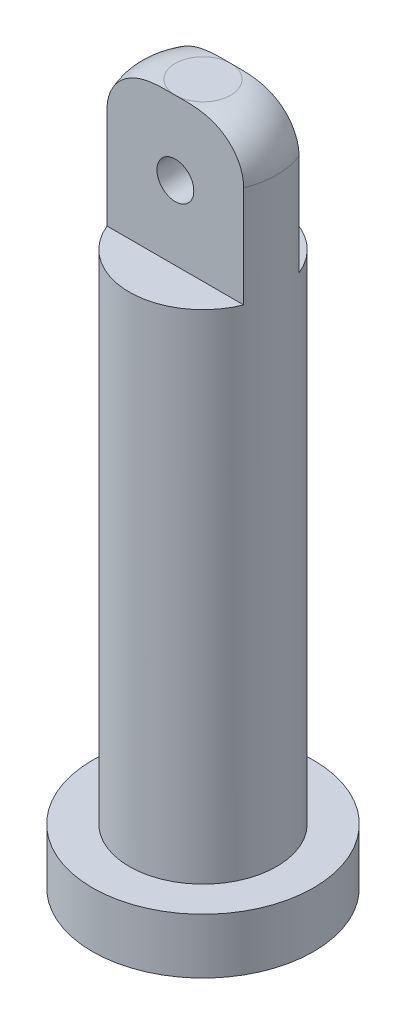
SolidWorks part; units mm, degrees
ref_plane "Front Plane" through (0, 0, 0) normal (0, 0, 1) x (1, 0, 0)
ref_plane "Top Plane" through (0, 0, 0) normal (0, 1, 0) x (1, 0, 0)
ref_plane "Right Plane" through (0, 0, 0) normal (1, 0, 0) x (0, 0, -1)
sketch "Sketch1" plane through (0, 0, 0) normal (0, 1, 0) x (1, 0, 0)
  circle A0 centre (0, 0) radius 3
  dimension "D1" = 6
extrude "Boss-Extrude1" add sketch "Sketch1" along normal blind 1.5
sketch "Sketch2" plane through (0, 1.5, 0) normal (0, 1, 0) x (1, 0, 0)
  circle A0 centre (0, 0) radius 2
  dimension "D1" = 4
extrude "Boss-Extrude2" add sketch "Sketch2" along normal blind 13.5
sketch "Sketch6" plane through (0, 15, 0) normal (0, 1, 0) x (1, 0, 0)
  line L1 (1.854, 0.75) -> (-1.854, 0.75)
  line L3 (1.854, -0.75) -> (-1.854, -0.75)
  line L5 (0, -0.75) -> (0, 0.75) construction
  line L6 (1.854, 0) -> (-1.854, 0) construction
  arc A0 (1.854, -0.75) -> (1.854, 0.75) centre (0, 0) ccw
  circle A1 centre (0, 0) radius 2
  arc A2 (-1.854, 0.75) -> (-1.854, -0.75) centre (0, 0) ccw
  dimension "D2" = 1.5
  dimension "D1" = 0
extrude "Boss-Extrude3" add sketch "Sketch6" along normal blind 4
sketch "Sketch7" plane through (0, 0, 0.75) normal (0, 0, 1) x (1, 0, 0)
  line L0 (0, 19) -> (0, 17) construction
  line L4 (-1.854, 15) -> (1.854, 15)
  line L5 (1.854, 15) -> (1.854, 19)
  line L6 (1.854, 19) -> (-1.854, 19)
  line L7 (-1.854, 19) -> (-1.854, 15)
  line L8 (-1.854, 15) -> (1.854, 15)
  line L9 (1.854, 15) -> (1.854, 19)
  line L10 (1.854, 19) -> (-1.854, 19)
  line L11 (-1.854, 19) -> (-1.854, 15)
  circle A0 centre (0, 17) radius 0.5
  dimension "D3" = 1
  dimension "D2" = 2
  dimension "D1" = 0
extrude "Cut-Extrude1" cut sketch "Sketch7" against normal blind 3 contours A0
fillet "Fillet5" radius 1.25 2 edges at (2, 19, 0) (-2, 19, 0)
